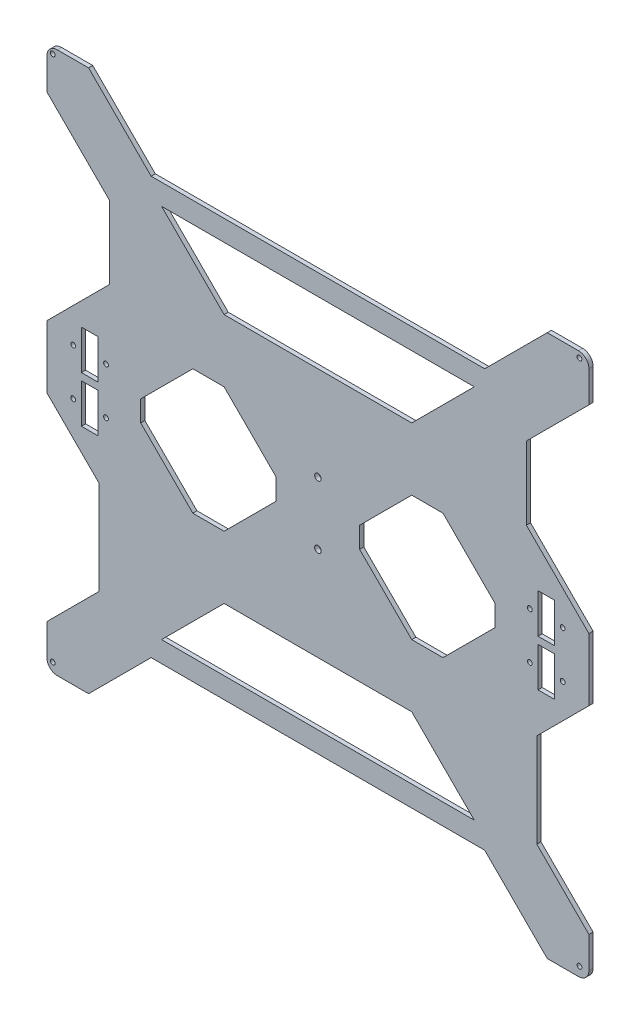
SolidWorks part; units mm, degrees
ref_plane "Front Plane" through (0, 0, 0) normal (0, 0, 1) x (1, 0, 0)
ref_plane "Top Plane" through (0, 0, 0) normal (0, 1, 0) x (1, 0, 0)
ref_plane "Right Plane" through (0, 0, 0) normal (1, 0, 0) x (0, 0, -1)
sketch "Model" plane through (0, 0, 0) normal (0, 0, 1) x (1, 0, 0)
  line L0 (38.5361, 132.6139) -> (38.5361, 132.4727)
  line L1 (38.5361, -178.6774) -> (38.5361, -178.7219)
  line L2 (-253.5639, -197.5861) -> (-253.5639, -197.7273)
  line L3 (-252.5813, 70.3317) -> (-252.5813, 25.8817)
  line L4 (-258.9313, -82.0683) -> (-258.9313, -139.2183)
  line L5 (38.5361, 132.6139) -> (38.5361, 132.4727)
  line L6 (38.5361, -178.6774) -> (38.5361, -178.7219)
  line L7 (7.7687, -139.2183) -> (7.7687, -82.0683)
  line L8 (1.4187, 25.8817) -> (1.4187, 70.3317)
  line L9 (-23.9813, 95.7317) -> (-227.1813, 95.7317)
  line L10 (-290.6813, 108.4317) -> (-252.5813, 70.3317)
  line L11 (-30.3313, -145.5683) -> (-68.4313, -107.4683)
  line L12 (-23.9813, -158.2683) -> (14.1187, -196.3683)
  line L13 (39.5187, 108.4317) -> (39.5187, 127.4817)
  line L14 (-227.1813, 95.7317) -> (-265.2813, 133.8317)
  line L15 (-220.8313, 83.0317) -> (-182.7313, 44.9317)
  line L16 (-274.6813, -45.4288) -> (-254.6813, -45.4288) construction
  line L17 (39.5187, -170.9683) -> (7.7687, -139.2183)
  line L18 (-265.2813, -196.3683) -> (-227.1813, -158.2683)
  line L19 (-182.7313, -107.4683) -> (-68.4313, -107.4683)
  line L20 (-264.6813, -45.4288) -> (-264.6813, -43.5832) construction
  line L21 (1.4187, 70.3317) -> (39.5187, 108.4317)
  line L22 (-23.9813, 95.7317) -> (14.1187, 133.8317)
  line L23 (-30.3313, 83.0317) -> (-68.4313, 44.9317)
  line L25 (-258.9313, -139.2183) -> (-290.6813, -170.9683)
  line L26 (-182.7313, 44.9317) -> (-68.4313, 44.9317)
  line L27 (-220.8313, -145.5683) -> (-182.7313, -107.4683)
  line L28 (-220.8313, -145.5683) -> (-30.3313, -145.5683)
  line L29 (-258.9313, -82.0683) -> (-290.6813, -50.3183)
  line L30 (-290.6813, -12.2183) -> (-290.6813, -50.3183)
  line L31 (-274.6813, -43.9683) -> (-274.6813, -31.2683) construction
  line L32 (-290.6813, -12.2183) -> (-252.5813, 25.8817)
  line L33 (-201.7813, -69.3683) -> (-233.5313, -37.6183)
  line L34 (-182.7313, -69.3683) -> (-201.7813, -69.3683)
  line L35 (1.4187, 25.8817) -> (39.5187, -12.2183)
  line L36 (39.5187, -12.2183) -> (39.5187, -50.3183)
  line L37 (-150.9813, -37.6183) -> (-182.7313, -69.3683)
  line L38 (39.5187, -50.3183) -> (22.4579, -67.3791)
  line L39 (22.4579, -67.3791) -> (7.7687, -82.0683)
  line L40 (-100.1813, -37.6183) -> (-100.1813, -24.9183)
  line L41 (-150.9813, -37.6183) -> (-150.9813, -24.9183)
  line L42 (-150.9813, -24.9183) -> (-182.7313, 6.8317)
  line L43 (-182.7313, 6.8317) -> (-201.7813, 6.8317)
  line L44 (-201.7813, 6.8317) -> (-233.5313, -24.9183)
  line L45 (-233.5313, -24.9183) -> (-233.5313, -37.6183)
  line L46 (-17.6313, -24.9183) -> (-17.6313, -37.6183)
  line L47 (-49.3813, 6.8317) -> (-17.6313, -24.9183)
  line L48 (-220.8313, 83.0317) -> (-30.3313, 83.0317)
  line L49 (-68.4313, 6.8317) -> (-49.3813, 6.8317)
  line L50 (-100.1813, -24.9183) -> (-68.4313, 6.8317)
  line L51 (-100.1813, -37.6183) -> (-68.4313, -69.3683)
  line L52 (-68.4313, -69.3683) -> (-49.3813, -69.3683)
  line L53 (-49.3813, -69.3683) -> (-17.6313, -37.6183)
  line L58 (-265.2813, -196.3683) -> (-284.3313, -196.3683)
  line L59 (-290.6813, -190.0183) -> (-290.6813, -170.9683)
  line L60 (-290.6813, 108.4317) -> (-290.6813, 127.4817)
  line L61 (-284.3313, 133.8317) -> (-265.2813, 133.8317)
  line L62 (14.1187, 133.8317) -> (33.1687, 133.8317)
  line L64 (39.5187, -170.9683) -> (39.5187, -190.0183)
  line L65 (33.1687, -196.3683) -> (14.1187, -196.3683)
  line L71 (-227.1813, -158.2683) -> (-23.9813, -158.2683)
  line L72 (38.5361, -178.6774) -> (38.5361, -178.7219)
  line L74 (-227.1813, -158.2683) -> (-23.9813, -158.2683)
  line L75 (38.5361, -178.6774) -> (38.5361, -178.7219)
  line L77 (-125.5813, 95.7317) -> (-125.5813, -158.2683) construction
  line L78 (-290.6813, -31.2683) -> (39.5187, -31.2683) construction
  arc A0 (33.1687, -196.3683) -> (39.5187, -190.0183) centre (33.1687, -190.0183) ccw
  arc A1 (-290.6813, -190.0183) -> (-284.3313, -196.3683) centre (-284.3313, -190.0183) ccw
  arc A2 (-290.6813, 127.4817) -> (-284.3313, 133.8317) centre (-284.3313, 127.4817) cw
  arc A3 (33.1687, 133.8317) -> (39.5187, 127.4817) centre (33.1687, 127.4817) cw
  circle A4 centre (-287.1253, -190.6025) radius 1.4605
  circle A5 centre (33.7529, -190.6025) radius 1.4605
  circle A6 centre (33.7529, 130.2757) radius 1.4605
  circle A7 centre (-287.1253, 130.2757) radius 1.4605
  circle A8 centre (-274.6813, -45.4288) radius 1.4605
  circle A9 centre (-254.6813, -45.4288) radius 1.4605
  circle A10 centre (23.5187, -45.4288) radius 1.4605
  circle A11 centre (3.5187, -45.4288) radius 1.4605
  circle A12 centre (23.5187, -17.1078) radius 1.4605
  circle A13 centre (3.5187, -17.1078) radius 1.4605
  circle A14 centre (-254.6813, -17.1078) radius 1.4605
  circle A15 centre (-274.6813, -17.1078) radius 1.4605
  circle A16 centre (-125.5813, -12.2183) radius 2
  circle A17 centre (-125.5813, -50.3183) radius 2
  point P72 (-125.5813, -31.2683)
  point P79 (-290.6813, -31.2683)
  point P114 (-125.5813, 83.0317)
  point P116 (39.5187, -31.2683)
  point P120 (-233.5313, -31.2683)
  point P129 (-150.9813, -31.2683)
  point P141 (-290.6813, -180.4933)
  point P149 (-125.5813, 44.9317)
  point P156 (-17.6313, -31.2683)
  dimension "D28" = 6.35
  dimension "D29" = 6.35
  dimension "D30" = 6.35
  dimension "D31" = 6.35
  dimension "D35" = 2.921
  dimension "D36" = 2.921
  dimension "D37" = 2.921
  dimension "D38" = 2.921
  dimension "D53" = 2.921
  dimension "D54" = 2.921
  dimension "D56" = 4
  dimension "D57" = 4
  dimension "D1" = 330.2
  dimension "D2" = 330.2
  dimension "D3" = 135
  dimension "D4" = 135
  dimension "D5" = 38.1
  dimension "D6" = 135
  dimension "D7" = 135
  dimension "D8" = 19.05
  dimension "D9" = 135
  dimension "D10" = 19.05
  dimension "D11" = 31.75
  dimension "D12" = 190.5
  dimension "D13" = 114.3
  dimension "D14" = 38.1
  dimension "D15" = 114.3
  dimension "D16" = 135
  dimension "D17" = 6.35
  dimension "D18" = 38.1
  dimension "D19" = 135
  dimension "D20" = 135
  dimension "D21" = 6.35
  dimension "D22" = 19.05
  dimension "D23" = 25.4
  dimension "D24" = 38.1
  dimension "D25" = 135
  dimension "D26" = 135
  dimension "D27" = 127
  dimension "D32" = 19.05
  dimension "D33" = 19.05
  dimension "D34" = 19.05
  dimension "D39" = 38.1
  dimension "D40" = 19.05
  dimension "D41" = 38.1
  dimension "D42" = 38.1
  dimension "D43" = 135
  dimension "D44" = 19.05
  dimension "D45" = 31.75
  dimension "D46" = 135
  dimension "D47" = 320.8782
  dimension "D48" = 320.8782
  dimension "D49" = 3.556
  dimension "D50" = 3.556
  dimension "D51" = 20
  dimension "D52" = 26
  dimension "D55" = 12.7
  dimension "D58" = 38.1
  dimension "D59" = 19.05
extrude "Boss-Extrude1" add sketch "Model" along normal mid plane 2.54 contours A3 L62 L22 L9 L14 L61 A2 L60 L10 L3 L32 L30 L29 L4 L25 L59 A1 L58 L18 L71 L12 L65 A0 L64 L17 L7 L39 L38 L36 L35 L8 L21 L13 A17 A16 A14 A13 A12 A10 A9 region at (-125.5808, -32.1456, 0)
sketch "Sketch1" plane through (0, 0, 1.27) normal (0, 0, 1) x (1, 0, 0)
  line L1 (-269.6813, -33.4288) -> (-259.6813, -33.4288)
  line L2 (-269.6813, -33.4288) -> (-269.6813, -57.4288)
  line L3 (-269.6813, -57.4288) -> (-259.6813, -57.4288)
  line L4 (-259.6813, -33.4288) -> (-259.6813, -57.4288)
  line L5 (-269.6813, -5.1078) -> (-259.6813, -5.1078)
  line L6 (-269.6813, -5.1078) -> (-269.6813, -29.1078)
  line L7 (-269.6813, -29.1078) -> (-259.6813, -29.1078)
  line L8 (-259.6813, -5.1078) -> (-259.6813, -29.1078)
  line L9 (8.5187, -5.1078) -> (18.5187, -5.1078)
  line L10 (8.5187, -5.1078) -> (8.5187, -29.1078)
  line L11 (8.5187, -29.1078) -> (18.5187, -29.1078)
  line L12 (18.5187, -5.1078) -> (18.5187, -29.1078)
  line L13 (8.5187, -33.4288) -> (18.5187, -33.4288)
  line L14 (8.5187, -33.4288) -> (8.5187, -57.4288)
  line L15 (8.5187, -57.4288) -> (18.5187, -57.4288)
  line L16 (18.5187, -33.4288) -> (18.5187, -57.4288)
  circle A1 centre (-274.6813, -45.4288) radius 1.4605 construction
  circle A5 centre (-274.6813, -17.1078) radius 1.4605 construction
  circle A7 centre (-254.6813, -17.1078) radius 1.4605 construction
  circle A8 centre (23.5187, -17.1078) radius 1.4605 construction
  circle A9 centre (23.5187, -45.4288) radius 1.4605 construction
  point P20 (-269.6813, -5.3478)
  dimension "D3" = 12
  dimension "D4" = 5
  dimension "D5" = 10
  dimension "D8" = 12
  dimension "D11" = 12
  dimension "D15" = 12
  dimension "D1" = 10
  dimension "D2" = 24
  dimension "D6" = 24
  dimension "D7" = 5
  dimension "D9" = 24
  dimension "D10" = 5
  dimension "D12" = 10
  dimension "D13" = 10
  dimension "D14" = 24
  dimension "D16" = 5
extrude "Cut-Extrude1" cut sketch "Sketch1" against normal blind 10
